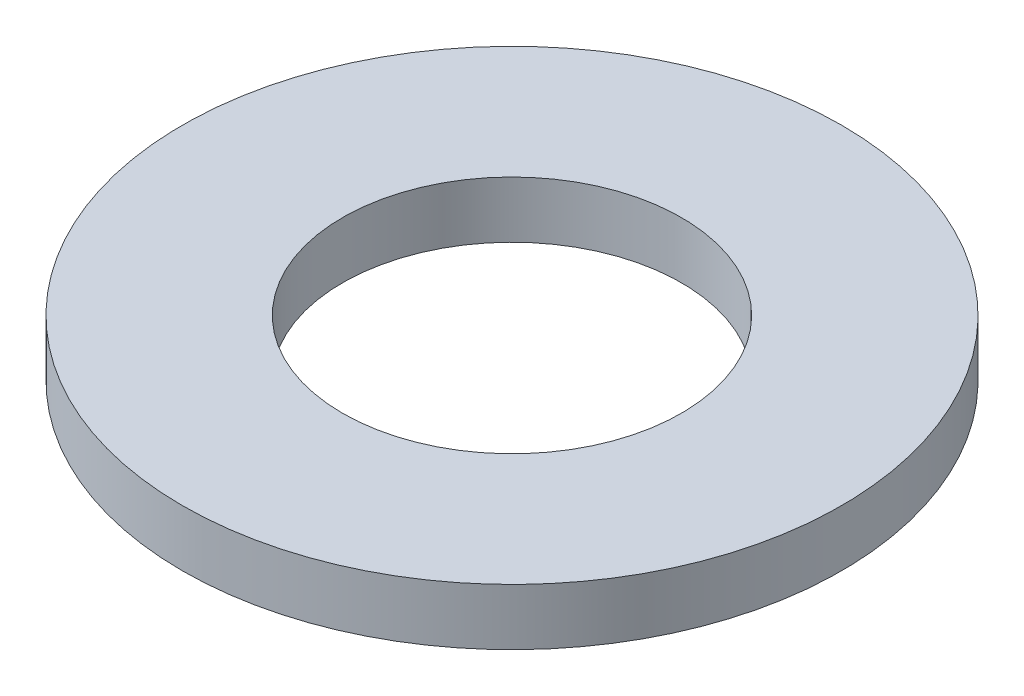
SolidWorks part; units mm, degrees
ref_plane "Front Plane" through (0, 0, 0) normal (0, 0, 1) x (1, 0, 0)
ref_plane "Top Plane" through (0, 0, 0) normal (0, 1, 0) x (1, 0, 0)
ref_plane "Right Plane" through (0, 0, 0) normal (1, 0, 0) x (0, 0, -1)
sketch "Sketch1" plane through (0, 0, 0) normal (0, 1, 0) x (1, 0, 0)
  circle A0 centre (0, 0) radius 87.5
  dimension "FLANGE_OD" = 175
extrude "Boss-Extrude1" add sketch "Sketch1" along normal blind 15
sketch "Sketch2" plane through (0, 0, 0) normal (0, 1, 0) x (1, 0, 0)
  circle A0 centre (0, 0) radius 45
  dimension "BORE_D" = 90
extrude "Cut-Extrude1" cut sketch "Sketch2" along normal through all
sketch "Sketch3" plane through (0, 15, 0) normal (0, 1, 0) x (1, 0, 0)
  circle A0 centre (0, 0) radius 32.1457 construction
  circle A1 centre (-32.1457, 0) radius 4.3305
  dimension "BOLT_D" = 8.661
  dimension "BOLT_PCD" = 64.2914
extrude "Cut-Extrude2" cut sketch "Sketch3" against normal blind 12.7263 rebuild error yes
pattern_circular "CirPattern1" count 3 over 360 rebuild error yes
